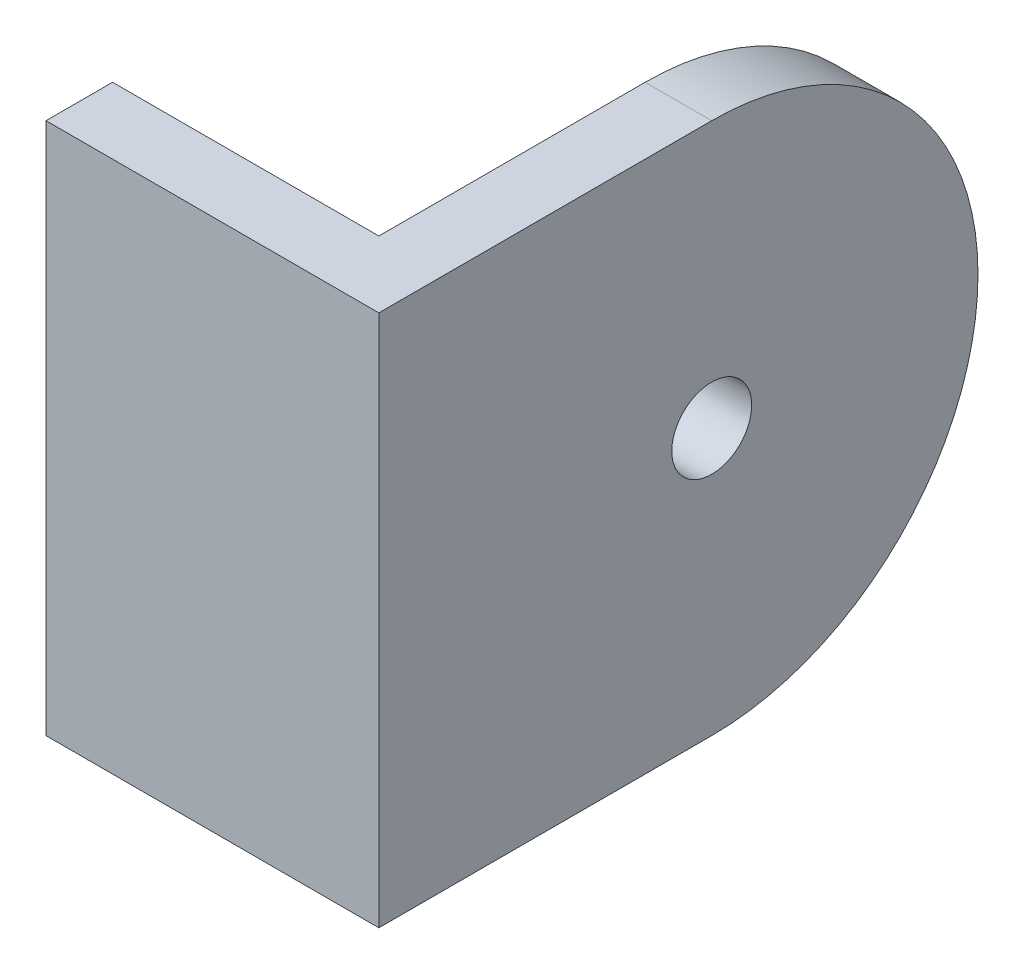
SolidWorks part; units mm, degrees
ref_plane "Front Plane" through (0, 0, 0) normal (0, 0, 1) x (1, 0, 0)
ref_plane "Top Plane" through (0, 0, 0) normal (0, 1, 0) x (1, 0, 0)
ref_plane "Right Plane" through (0, 0, 0) normal (1, 0, 0) x (0, 0, -1)
sketch "Sketch1" plane through (0, 0, 0) normal (0, 1, 0) x (1, 0, 0)
  line L4 (-4.4181, 15.2015) -> (0.5819, 15.2015)
  line L5 (0.5819, 15.2015) -> (0.5819, -29.7985)
  line L6 (0.5819, -29.7985) -> (-24.4181, -29.7985)
  line L7 (-24.4181, -29.7985) -> (-24.4181, -24.7985)
  line L8 (-24.4181, -24.7985) -> (-4.4181, -24.7985)
  line L9 (-4.4181, -24.7985) -> (-4.4181, 15.2015)
extrude "Boss-Extrude1" add sketch "Sketch1" along normal mid plane 40
sketch "Sketch2" plane through (-4.4181, 0, 0) normal (-1, 0, 0) x (0, 0, 1)
  circle A2 centre (4.7985, 0) radius 3
fillet "Fillet1" radius 20 1 edges at (-1.9181, -20, -15.2015)
fillet "Fillet2" radius 20 1 edges at (-1.9181, 20, -15.2015)
extrude "Cut-Extrude2" cut sketch "Sketch2" against normal blind 40
